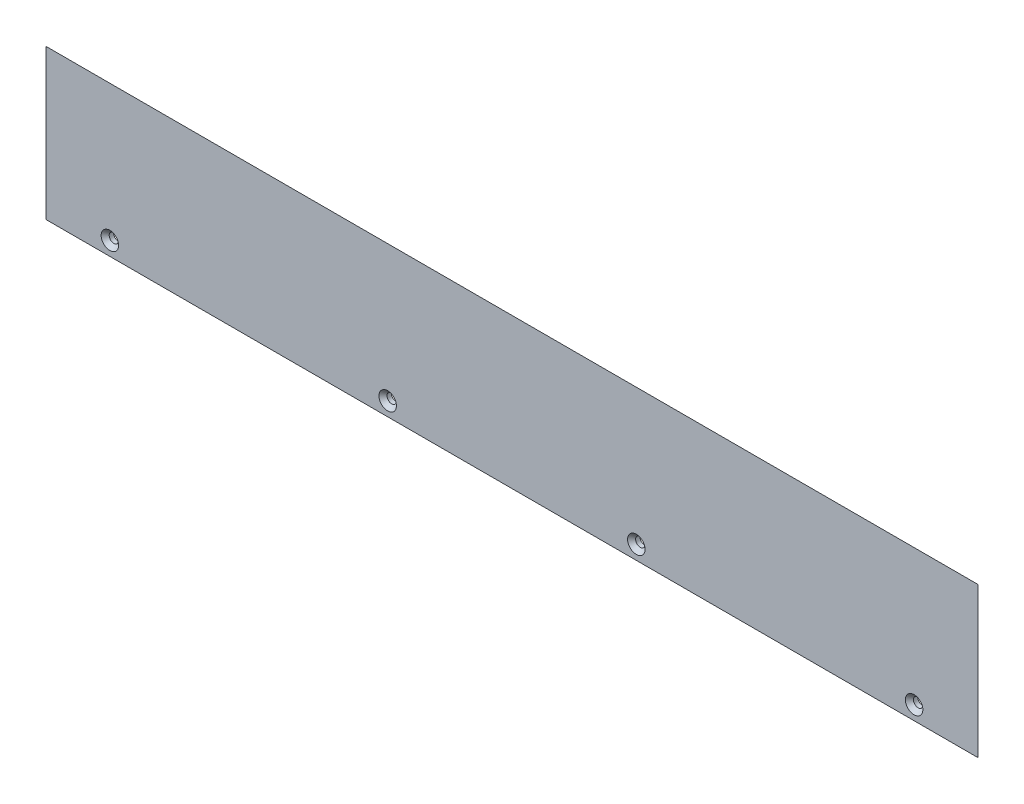
SolidWorks part; units mm, degrees
ref_plane "Front Plane" through (0, 0, 0) normal (0, 0, 1) x (1, 0, 0)
ref_plane "Top Plane" through (0, 0, 0) normal (0, 1, 0) x (1, 0, 0)
ref_plane "Right Plane" through (0, 0, 0) normal (1, 0, 0) x (0, 0, -1)
sketch "Sketch1" plane through (0, 0, 0) normal (0, 0, 1) x (1, 0, 0)
  line L1 (0, 0) -> (335.5, 0)
  line L2 (0, 0) -> (0, 54)
  line L3 (0, 54) -> (335.5, 54)
  line L4 (335.5, 0) -> (335.5, 54)
  dimension "D1" = 54
  dimension "D2" = 335.5
extrude "Boss-Extrude1" add sketch "Sketch1" along normal blind 3
chamfer "Chamfer1" distance 3 angle 45 3 edges at (0, 27, 0) (167.75, 54, 0) (335.5, 27, 0)
sketch "Sketch2" plane through (0, 0, 3) normal (0, 0, 1) x (1, 0, 0)
  line L0 (0, 5) -> (335.5, 5) construction
  line L1 (0, 54) -> (0, 0) construction
  line L2 (335.5, 0) -> (335.5, 54) construction
  line L3 (0, 0) -> (335.5, 0) construction
  point P8 (123, 5)
  point P9 (23, 5)
  point P10 (212.5, 5)
  point P11 (312.5, 5)
  dimension "D1" = 5
  dimension "D2" = 23
  dimension "D3" = 100
  dimension "D4" = 23
  dimension "D5" = 100
hole_wizard "CSK for M3 Flat Head Machine Screw1" positions "Sketch4" profile "Sketch3" countersink size "M3" standard "ANSI Metric" end condition through all
sketch "Sketch4" plane through (0, 0, 3) normal (0, 0, 1) x (1, 0, 0)
  point P0 (23, 5)
  point P3 (123, 5)
  point P6 (212.5, 5)
  point P9 (312.5, 5)
sketch "Sketch3" plane through (23, 5, 3) normal (1, 0, 0) x (0, -1, 0)
  line L0 (0, 0) -> (0, 3)
  line L1 (0, 3) -> (1.7, 3)
  line L2 (1.7, 3) -> (1.7, 1.45)
  line L3 (1.7, 1.45) -> (3.15, 0)
  line L5 (3.15, 0) -> (0, 0)
  line L6 (-1.7, 1.45) -> (-3.15, 0) construction
  line L11 (0, -6.35) -> (0, 107.95) construction
  dimension "Thru Hole Dia." = 3.4
  dimension "Thru Hole Depth" = 3
  dimension "Near C'Sink Dia." = 6.3
  dimension "Near C'Sink Angle" = 90
